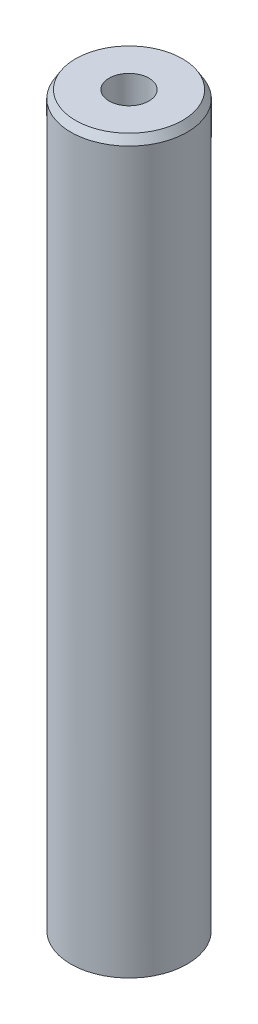
SolidWorks part; units mm, degrees
ref_plane "Front Plane" through (0, 0, 0) normal (0, 0, 1) x (1, 0, 0)
ref_plane "Top Plane" through (0, 0, 0) normal (0, 1, 0) x (1, 0, 0)
ref_plane "Right Plane" through (0, 0, 0) normal (1, 0, 0) x (0, 0, -1)
sketch "Sketch1" plane through (0, 0, 0) normal (0, 1, 0) x (1, 0, 0)
  circle A0 centre (0, 0) radius 12.5
  dimension "SHAFT_OD" = 25
extrude "Boss-Extrude1" add sketch "Sketch1" along normal blind 157.4517
sketch "Sketch2" plane through (0, 0, 0) normal (0, 1, 0) x (1, 0, 0)
  circle A0 centre (0, 0) radius 4.2744
  dimension "BORE_D" = 8.5488
extrude "Cut-Extrude1" cut sketch "Sketch2" along normal through all
chamfer "Chamfer1" distance 1.6808 angle 31.135 2 edges at (0, 157.4517, 12.5) (0, 0, 12.5) first distance on face at (0, 157.4517, 12.5) first distance on face at (0, 0, 4.2744)
